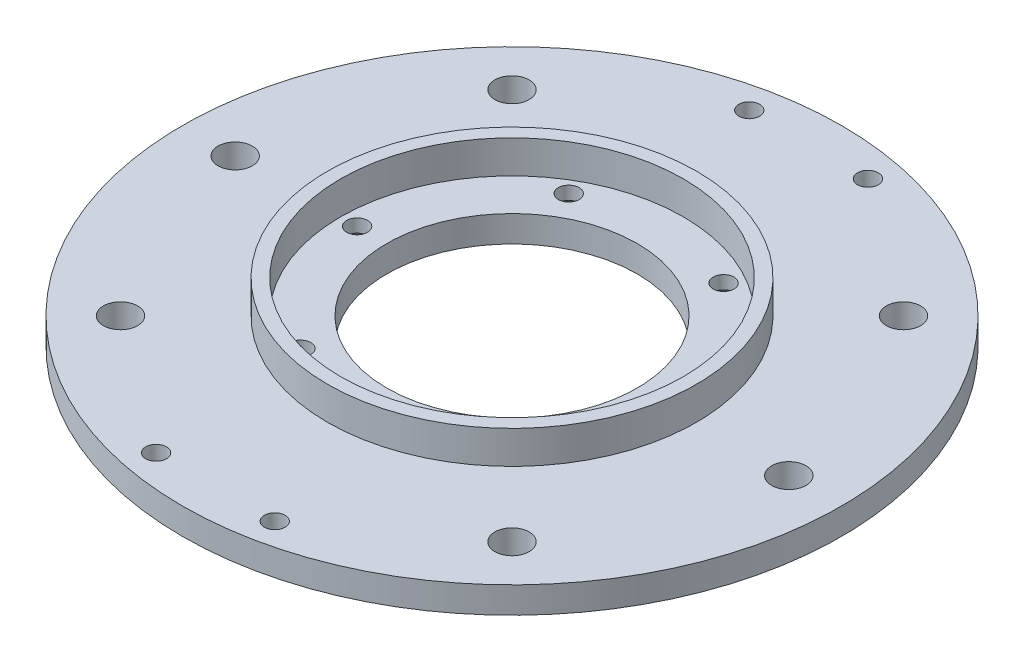
SolidWorks part; units mm, degrees
material "1060 Сплав"
ref_plane "Спереди" through (0, 0, 0) normal (0, 0, 1) x (1, 0, 0)
ref_plane "Сверху" through (0, 0, 0) normal (0, 1, 0) x (1, 0, 0)
ref_plane "Справа" through (0, 0, 0) normal (1, 0, 0) x (0, 0, -1)
sketch "Эскиз1" plane through (0, 0, 0) normal (0, 1, 0) x (1, 0, 0)
  circle A0 centre (0, 0) radius 19
  circle A1 centre (0, 0) radius 50
  dimension "D1" = 38
  dimension "D2" = 100
extrude "Бобышка-Вытянуть1" add sketch "Эскиз1" along normal blind 4
hole_wizard "Сверло под метчик  спиральное M31" positions "Эскиз2" profile "Эскиз3" hole size "M3x0.5" standard "DIN"
sketch "Эскиз2" plane through (0, 4, 0) normal (0, 1, 0) x (1, 0, 0)
  point P0 (23.5, 0)
  dimension "D1" = 23.5
sketch "Эскиз3" plane through (23.5, 4, 0) normal (1, 0, 0) x (0, 0, 1)
  line L0 (0, 0) -> (0, 8.9464)
  line L1 (0, 8.9464) -> (1.575, 8)
  line L2 (1.575, 8) -> (1.575, 0)
  line L5 (1.575, 0) -> (0, 0)
  line L10 (0, 8.9464) -> (-1.575, 8) construction
  line L11 (0, -6.35) -> (0, 107.95) construction
  dimension "Диаметр отверстия" = 3.15
  dimension "Глубина отверстия" = 8
  dimension "Угол заточки сверла" = 118
pattern_circular "Круговой массив1" count 6 over 360 about axis through (0, 4, 0) along (0, 1, 0) of "Сверло под метчик  спиральное M31"
chamfer "Фаска1" distance 2 angle 45 6 edges at (-11.75, 0, 21.9266) (-23.5, 0, 1.575) (-11.75, 0, -18.7766) (11.75, 0, -18.7766) (23.5, 0, 1.575) (11.75, 0, 21.9266)
hole_wizard "Сверло под метчик  спиральное M32" positions "Эскиз4" profile "Эскиз5" hole size "M3x0.5" standard "DIN" end condition through all
sketch "Эскиз4" plane through (0, 0, 0) normal (0, -1, 0) x (-1, 0, 0)
  point P0 (-9, -45)
  dimension "D1" = 9
  dimension "D2" = 45
sketch "Эскиз5" plane through (9, 0, 45) normal (1, 0, 0) x (0, 0, -1)
  line L0 (0, 0) -> (0, 4)
  line L1 (0, 4) -> (1.575, 4)
  line L2 (1.575, 4) -> (1.575, 0)
  line L5 (1.575, 0) -> (0, 0)
  line L11 (0, -6.35) -> (0, 107.95) construction
  dimension "Диаметр сквозного отверстия" = 3.15
  dimension "Глубина сквозного отверстия" = 4
sketch "Эскиз6" plane through (0, 0, 0) normal (0, 1, 0) x (1, 0, 0)
  line L0 (0, 0) -> (0, 15.2777) construction
  line L1 (0, 0) -> (-12.2514, 0) construction
pattern_linear "Линейный массив1" count 2 spacing 18 along (-1, 0, 0) count 2 spacing 90 along (0, 0, -1) of "Сверло под метчик  спиральное M32"
hole_wizard "Сверло под метчик  спиральное M52" positions "Эскиз11" profile "Эскиз12" hole size "M5x0.8" standard "DIN" end condition through all
sketch "Эскиз11" plane through (0, 0, 0) normal (0, -1, 0) x (-1, 0, 0)
  point P0 (42, 0)
  point P2 (-42, 0)
  dimension "D1" = 42
  dimension "D2" = 42
sketch "Эскиз12" plane through (-42, 0, 0) normal (1, 0, 0) x (0, 0, -1)
  line L0 (0, 0) -> (0, 4)
  line L1 (0, 4) -> (2.6, 4)
  line L2 (2.6, 4) -> (2.6, 0)
  line L5 (2.6, 0) -> (0, 0)
  line L11 (0, -6.35) -> (0, 107.95) construction
  dimension "Диаметр сквозного отверстия" = 5.2
  dimension "Глубина сквозного отверстия" = 4
pattern_circular "Круговой массив3" count 2 every 45 about axis through (0, 0, 0) along (0, 1, 0) of "Сверло под метчик  спиральное M52" other way count 2
sketch "Эскиз14" plane through (0, 4, 0) normal (0, 1, 0) x (1, 0, 0)
  circle A0 centre (0, 0) radius 26
  circle A1 centre (0, 0) radius 28
  dimension "D1" = 52
  dimension "D2" = 56
extrude "Бобышка-Вытянуть2" add sketch "Эскиз14" along normal blind 5
